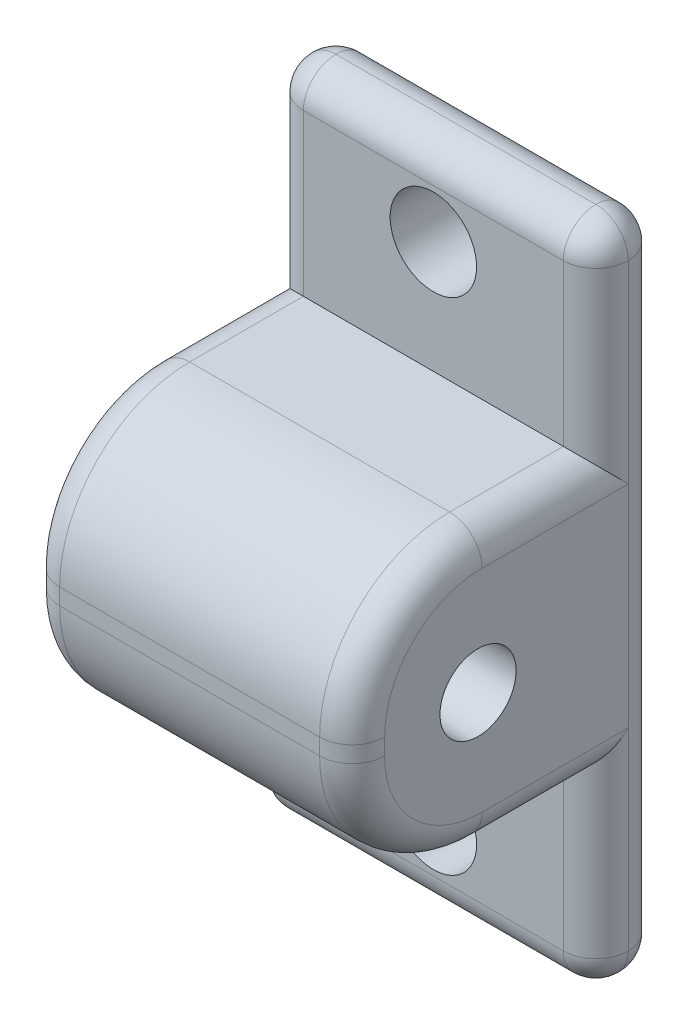
SolidWorks part; units mm, degrees
note: '?' marks a value the reader was unsure of.
ref_plane "Front" through (0, 0, 0) normal (0, 0, 1) x (1, 0, 0)
ref_plane "Top" through (0, 0, 0) normal (0, 1, 0) x (1, 0, 0)
ref_plane "Right" through (0, 0, 0) normal (1, 0, 0) x (0, 0, -1)
ref_axis "Axis1" through (0, 0, 55) along (0, 0, -1)?
sketch "Sketch1" plane through (0, 0, 0) normal (1, 0, 0) x (0, 0, -1)
  line L0 (0, 0) -> (0, 25.908)
  line L1 (0, 25.908) -> (-5.08, 25.908)
  line L2 (-5.08, 25.908) -> (-5.08, 10.795)
  line L3 (-5.08, 10.795) -> (-13.97, 10.795)
  line L4 (-24.13, 0.635) -> (-24.13, -0.635)
  line L5 (-13.97, -10.795) -> (-5.08, -10.795)
  line L6 (-5.08, -10.795) -> (-5.08, -25.908)
  line L7 (-5.08, -25.908) -> (0, -25.908)
  line L8 (0, -25.908) -> (0, 0)
  arc A0 (-13.97, -10.795) -> (-24.13, -0.635) centre (-13.97, -0.635) cw
  arc A1 (-24.13, 0.635) -> (-13.97, 10.795) centre (-13.97, 0.635) cw
  point P12 (-24.13, -10.795)
  point P15 (-24.13, 10.795)
  dimension "D5" = 10.16
  dimension "D1" = 25.908
  dimension "D2" = 5.08
  dimension "D3" = 19.05
  dimension "D4" = 21.59
extrude "Boss-Extrude1" add sketch "Sketch1" against normal blind 25.4
sketch "Sketch2" plane through (-25.4, 0, 0) normal (-1, 0, 0) x (0, 0, 1)
  line L0 (5.08, -10.795) -> (5.08, 10.795)
  line L9 (0, 25.908) -> (0, -25.908)
  line L10 (0, -25.908) -> (5.08, -25.908)
  line L11 (5.08, -25.908) -> (5.08, -10.795)
  line L12 (5.08, -10.795) -> (13.97, -10.795)
  line L13 (24.13, -0.635) -> (24.13, 0.635)
  line L14 (13.97, 10.795) -> (5.08, 10.795)
  line L15 (5.08, 10.795) -> (5.08, 25.908)
  line L16 (5.08, 25.908) -> (0, 25.908)
  line L20 (5.08, -10.795) -> (13.97, -10.795)
  line L21 (24.13, -0.635) -> (24.13, 0.635)
  line L22 (13.97, 10.795) -> (5.08, 10.795)
  arc A2 (13.97, -10.795) -> (24.13, -0.635) centre (13.97, -0.635) ccw
  arc A3 (24.13, 0.635) -> (13.97, 10.795) centre (13.97, 0.635) ccw
  arc A4 (13.97, -10.795) -> (24.13, -0.635) centre (13.97, -0.635) ccw
  arc A5 (24.13, 0.635) -> (13.97, 10.795) centre (13.97, 0.635) ccw
  dimension "D1" = 0
hole_wizard "15/64 (0.23438) Diameter Hole1" positions "Sketch3" profile "Sketch4" hole size "15/64" standard "ANSI Inch"
sketch "Sketch3" plane through (0, 0, 0) normal (1, 0, 0) x (0, 0, -1)
  line L0 (0, 0) -> (-24.13, 0) construction
  line L1 (0, -25.908) -> (0, 25.908) construction
  line L2 (-24.13, 0.635) -> (-24.13, -0.635) construction
  point P0 (-14.2875, 0)
  dimension "D1" = 14.2875
sketch "Sketch4" plane through (0, 0, 14.2875) normal (0, 1, 0) x (0, 0, -1)
  line L0 (0, 0) -> (0, 27.1885)
  line L1 (0, 27.1885) -> (2.9766, 25.4)
  line L2 (2.9766, 25.4) -> (2.9766, 0)
  line L5 (2.9766, 0) -> (0, 0)
  line L10 (0, 27.1885) -> (-2.9766, 25.4) construction
  line L11 (0, -6.35) -> (0, 107.95) construction
  dimension "Hole Dia." = 5.9533
  dimension "Hole Depth" = 25.4
  dimension "Drill Angle" = 118
hole_wizard "1/4 Clearance Hole1" positions "Sketch5" profile "Sketch6" hole size "1/4" standard "ANSI Inch"
sketch "Sketch5" plane through (0, 0, 5.08) normal (0, 0, 1) x (1, 0, 0)
  line L0 (-12.7, 19.558) -> (-12.7, -19.558) construction
  line L2 (0, -2.9766) -> (0, 2.9766) construction
  line L3 (0, -10.795) -> (0, -25.908) construction
  line L4 (-25.4, 25.908) -> (0, 25.908) construction
  line L5 (-25.4, 0) -> (0, 0) construction
  line L7 (-25.4, -10.795) -> (-25.4, 10.795) construction
  circle A0 centre (-12.7, 19.558) radius 6.35 construction
  point P0 (-12.7, 19.558)
  point P2 (-12.7, -19.558)
  dimension "D2" = 12.7
  dimension "D1" = 12.7
sketch "Sketch6" plane through (-12.7, 19.558, 5.08) normal (1, 0, 0) x (0, -1, 0)
  line L0 (0, 0) -> (0, 27.4298)
  line L1 (0, 27.4298) -> (3.3782, 25.4)
  line L2 (3.3782, 25.4) -> (3.3782, 0)
  line L5 (3.3782, 0) -> (0, 0)
  line L10 (0, 27.4298) -> (-3.3782, 25.4) construction
  line L11 (0, -6.35) -> (0, 107.95) construction
  dimension "Hole Dia." = 6.7564
  dimension "Hole Depth" = 25.4
  dimension "Drill Angle" = 118
fillet "Fillet1" radius 2.54 20 edges at (0, 10.795, 9.525) (0, 7.8192, 21.1542) (0, 0, 24.13) (0, -10.795, 9.525) (-25.4, 10.795, 9.525) (-25.4, -10.795, 9.525) (-25.4, -7.8192, 21.1542) (-25.4, 0, 24.13) (-12.7, -25.908, 0) (-25.4, -25.908, 2.54) (-12.7, -25.908, 5.08) (-12.7, 25.908, 5.08) (-12.7, 25.908, 0) (0, 0, 0) (0, -18.3515, 5.08) (0, 18.3515, 5.08) (0, -7.8192, 21.1542) (-25.4, 0, 0) (-25.4, 18.3515, 5.08) (-25.4, 7.8192, 21.1542)
